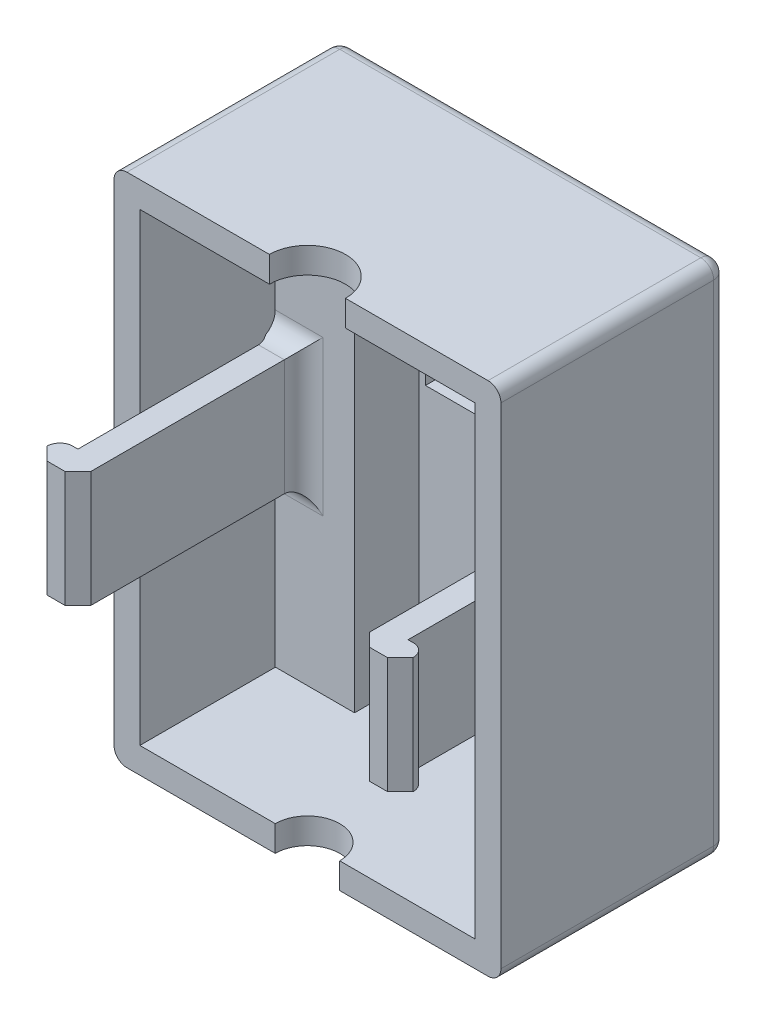
SolidWorks part; units mm, degrees
ref_plane "Front Plane" through (0, 0, 0) normal (0, 0, 1) x (1, 0, 0)
ref_plane "Top Plane" through (0, 0, 0) normal (0, 1, 0) x (1, 0, 0)
ref_plane "Right Plane" through (0, 0, 0) normal (1, 0, 0) x (0, 0, -1)
sketch "Sketch1" plane through (0, 0, 0) normal (0, 0, 1) x (1, 0, 0)
  line L1 (-15, 20) -> (15, 20)
  line L2 (-15, 20) -> (-15, -20)
  line L3 (-15, -20) -> (15, -20)
  line L4 (15, 20) -> (15, -20)
  line L5 (-15, 20) -> (15, -20) construction
  line L6 (-15, -20) -> (15, 20) construction
  point P0 (0, 0)
  dimension "D1" = 40
  dimension "D2" = 30
extrude "Boss-Extrude1" add sketch "Sketch1" along normal blind 17.5
sketch "Sketch2" plane through (0, 0, 17.5) normal (0, 0, 1) x (1, 0, 0)
  line L0 (15, -20) -> (15, 20) construction
  line L1 (-13, 18) -> (13, 18)
  line L2 (-13, 18) -> (-13, -18)
  line L3 (-13, -18) -> (13, -18)
  line L4 (13, 18) -> (13, -18)
  line L5 (-13, 18) -> (13, -18) construction
  line L6 (-13, -18) -> (13, 18) construction
  line L7 (-15, -20) -> (15, -20) construction
  point P0 (0, 0)
  dimension "D1" = 2
  dimension "D2" = 2
extrude "Cut-Extrude1" cut sketch "Sketch2" against normal blind 15.5
sketch "Sketch3" plane through (0, 0, 2) normal (0, 0, 1) x (1, 0, 0)
  line L0 (0, 18) -> (6.85, 18)
  line L1 (13, 18) -> (-13, 18) construction
  line L2 (0, 18) -> (-6.85, 18)
  line L3 (0, 18) -> (0, 15.75)
  line L4 (-6.85, 18) -> (6.85, 18)
  line L5 (-6.85, 18) -> (-6.85, -14)
  line L6 (-6.85, -14) -> (6.85, -14)
  line L7 (6.85, 18) -> (6.85, -14)
  line L8 (0, 15.75) -> (-6.35, 15.75)
  line L9 (0, 15.75) -> (6.35, 15.75)
  line L10 (-6.35, 15.75) -> (-6.35, 1.75)
  line L11 (6.35, 15.75) -> (6.35, 1.75)
  line L12 (6.35, 1.75) -> (-6.35, 1.75)
  line L13 (6.85, -14) -> (5.05, -14)
  line L14 (-13, 18) -> (-13, -18) construction
  line L15 (-6.85, 18) -> (-13, 18)
  line L16 (-6.85, 18) -> (-6.85, -17.9856)
  line L17 (-6.85, -17.9856) -> (-13, -17.9856)
  line L18 (-13, 18) -> (-13, -17.9856)
  line L20 (6.85, 18) -> (13, 18)
  line L21 (6.85, 18) -> (6.85, -18)
  line L22 (6.85, -18) -> (13, -18)
  line L23 (13, 18) -> (13, -18)
  circle A0 centre (5.05, -6.6) radius 1.6
  line M8 (13, -18) -> (13, 18)
  line M9 (13, 18) -> (-13, 18)
  line M10 (-13, 18) -> (-13, -18)
  line M11 (-13, -18) -> (13, -18)
  dimension "D10" = 3.2
  dimension "D1" = 6.85
  dimension "D2" = 6.85
  dimension "D3" = 32
  dimension "D4" = 2.25
  dimension "D5" = 6.35
  dimension "D6" = 6.35
  dimension "D7" = 14
  dimension "D8" = 1.8
  dimension "D9" = 7.4
extrude "Cut-Extrude2" cut sketch "Sketch3" against normal through all contours L12 L11 L9 L8 L10 | A0 region at (0, 8.75, 2) region at (5.05, -6.6, 2)
extrude "Boss-Extrude2" add sketch "Sketch3<3>" along normal blind 5 contours L17 L16 L5 M9 M10 | L7 L21 M11 M8 M9 region at (9.925, 0, 2) region at (-9.925, 0.0072, 2)
sketch "Sketch3<3>" plane through (0, 0, 2) normal (0, 0, 1) x (1, 0, 0) same geometry as "Sketch3"
sketch "Sketch4" plane through (0, 18, 0) normal (0, -1, 0) x (1, 0, 0)
  line L0 (13, 17.5) -> (-13, 17.5) construction
  line L1 (-2.95, 17.5) -> (2.95, 17.5)
  arc A0 (-2.95, 17.5) -> (2.95, 17.5) centre (0, 17.5) ccw
  dimension "D1" = 5.9
extrude "Cut-Extrude3" cut sketch "Sketch4" against normal through all
sketch "Sketch5" plane through (0, -18, 0) normal (0, 1, 0) x (1, 0, 0)
  line L0 (-13, -17.5) -> (13, -17.5) construction
  line L1 (-2.5, -17.5) -> (2.5, -17.5)
  arc A0 (2.5, -17.5) -> (-2.5, -17.5) centre (0, -17.5) ccw
  dimension "D1" = 5
extrude "Cut-Extrude4" cut sketch "Sketch5" against normal through all
sketch "Sketch6" plane through (13, 0, 0) normal (-1, 0, 0) x (0, 0, 1)
  line L0 (17.5, -18) -> (17.5, 18) construction
  line L1 (17.5, 4.5) -> (7, 4.5)
  line L3 (17.5, -4.5) -> (7, -4.5)
  line L4 (7, 4.5) -> (7, -4.5)
  line L6 (17.5, -4.5) -> (24.5, -4.5)
  line L7 (17.5, 4.5) -> (24.5, 4.5)
  line L9 (17.5, -4.5) -> (24.5, -4.5)
  line L11 (24.5, -4.5) -> (24.5, 4.5)
  point P0 (17.5, 0)
  line M5 (7, 18) -> (7, -18)
  line M7 (17.5, -18) -> (17.5, 18)
  dimension "D1" = 9
  dimension "D3" = 4.5
  dimension "D4" = 7
extrude "Boss-Extrude3" add sketch "Sketch6" along normal blind 2 from offset 0.2 contours L6 L11 L7 M7 | L3 L1 M7 M5 region at (13, 0, 12.25) region at (13, 0, 21)
sketch "Sketch7" plane through (-13, 0, 0) normal (1, 0, 0) x (0, 0, -1)
  line L0 (-17.5, 18) -> (-17.5, -18) construction
  line L1 (-17.5, -4.5) -> (-7, -4.5)
  line L3 (-17.5, 4.5) -> (-7, 4.5)
  line L6 (-17.5, 4.5) -> (-24.5, 4.5)
  line L7 (-7, 18) -> (-7, -17.9856) construction
  line L8 (-17.5, -4.5) -> (-24.5, -4.5)
  line L10 (-17.5, 4.5) -> (-24.5, 4.5)
  line L12 (-24.5, 4.5) -> (-24.5, -4.5)
  point P0 (-17.5, 0)
  line M6 (-7, -17.9856) -> (-7, 18)
  line M8 (-17.5, 18) -> (-17.5, -18)
  dimension "D1" = 9
  dimension "D3" = 4.5
fillet "Fillet2" radius 1 8 edges at (15, -20, 8.75) (15, 20, 8.75) (-15, 20, 8.75) (-15, -20, 8.75) (0, -20, 0) (0, 20, 0) (-15, 0, 0) (15, 0, 0)
extrude "Boss-Extrude7" add sketch "Sketch7" along normal blind 2 from offset 0.2 contours L8 L10 M8 | L3 L1 M8 M6 region at (-13, 0, 12.25) region at (-13, 0, 21)
sketch "Sketch8" plane through (-12.8, 0, 0) normal (-1, 0, 0) x (0, 0, 1)
  line L5 (7, -4.5) -> (24.5, -4.5) construction
  line L6 (24.5, 4.5) -> (22.5, 4.5)
  line L7 (24.5, 4.5) -> (24.5, -4.5)
  line L8 (24.5, -4.5) -> (22.5, -4.5)
  line L9 (22.5, 4.5) -> (22.5, -4.5)
  dimension "D1" = 2
extrude "Boss-Extrude8" add sketch "Sketch8" along normal blind 1.4
fillet "Fillet6" radius 1.5 8 edges at (-12.8, 0, 7) (-11.8, -4.5, 7) (-10.8, 0, 7) (-11.8, 4.5, 7) (11.8, 4.5, 7) (11.8, -4.5, 7) (12.8, 0, 7) (10.8, 0, 7)
sketch "Sketch9" plane through (12.8, 0, 0) normal (1, 0, 0) x (0, 0, -1)
  line L0 (-8.5, 4.5) -> (-24.5, 4.5) construction
  line L1 (-24.5, 4.5) -> (-22.5, 4.5)
  line L2 (-24.5, 4.5) -> (-24.5, -4.5)
  line L3 (-24.5, -4.5) -> (-22.5, -4.5)
  line L4 (-22.5, 4.5) -> (-22.5, -4.5)
  line L5 (-24.5, -4.5) -> (-24.5, 4.5) construction
  line L6 (-8.5, -4.5) -> (-24.5, -4.5) construction
  dimension "D1" = 2
extrude "Boss-Extrude9" add sketch "Sketch9" along normal blind 1.4
chamfer "Chamfer1" distance 1 angle 45 4 edges at (-10.8, 0, 24.5) (-14.2, 0, 24.5) (10.8, 0, 24.5) (14.2, 0, 24.5)
fillet "Fillet7" radius 1 2 edges at (-14.2, 0, 22.5) (14.2, 0, 22.5)
